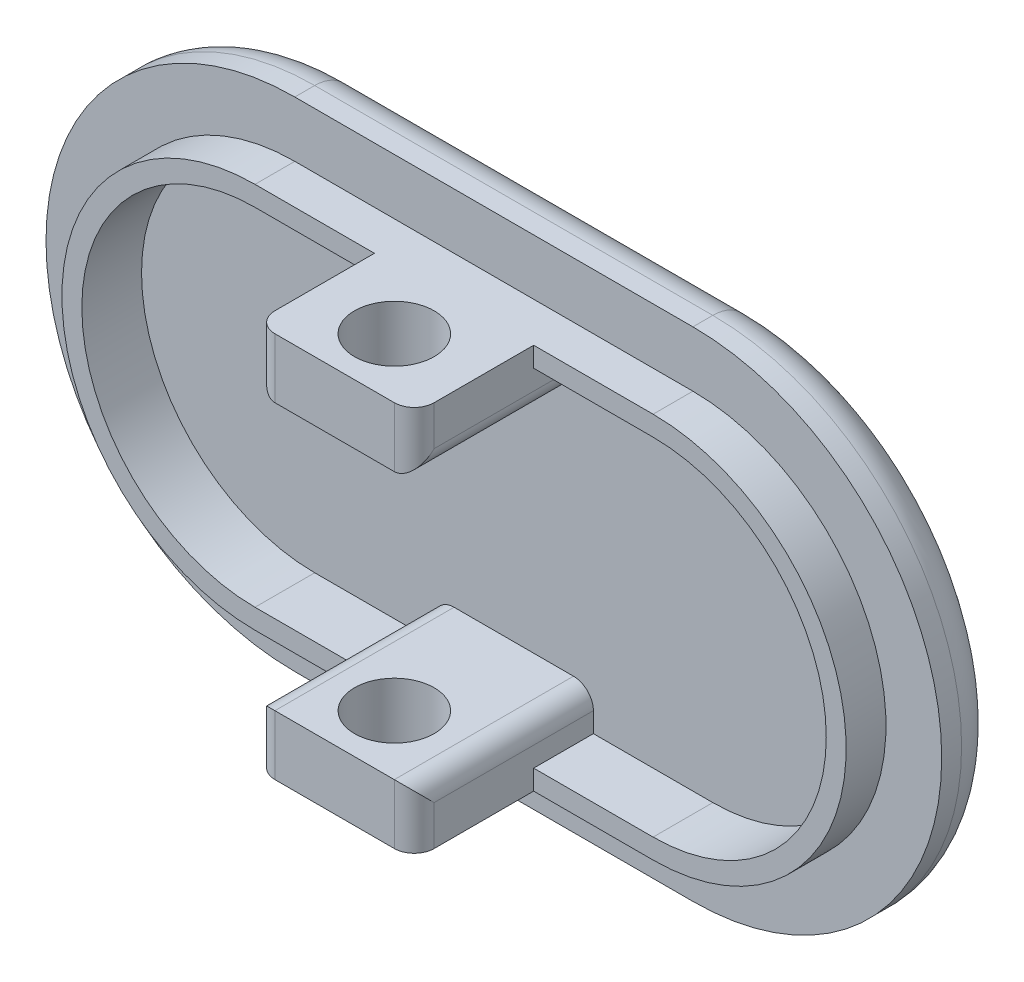
SolidWorks part; units mm, degrees
ref_plane "Plano frontal" through (0, 0, 0) normal (0, 0, 1) x (1, 0, 0)
ref_plane "Plano superior" through (0, 0, 0) normal (0, 1, 0) x (1, 0, 0)
ref_plane "Plano direito" through (0, 0, 0) normal (1, 0, 0) x (0, 0, -1)
sketch "Esboço1" plane through (0, 0, 0) normal (0, 0, 1) x (1, 0, 0)
  line L0 (-10, 0) -> (10, 0) construction
  line L1 (-10, 9.7) -> (10, 9.7)
  line L2 (-10, -9.7) -> (10, -9.7)
  line L3 (-10, 12.5) -> (10, 12.5)
  line L4 (-10, -12.5) -> (10, -12.5)
  arc A0 (-10, 9.7) -> (-10, -9.7) centre (-10, 0) ccw
  arc A1 (10, -9.7) -> (10, 9.7) centre (10, 0) ccw
  arc A2 (10, -12.5) -> (10, 12.5) centre (10, 0) ccw
  arc A3 (-10, 12.5) -> (-10, -12.5) centre (-10, 0) ccw
  point P2 (0, 0)
  dimension "D2" = 9.7
  dimension "D1" = 12.5
  dimension "D3" = 20
extrude "Ressalto-extrusão1" add sketch "Esboço1" along normal blind 3
extrude "Ressalto-extrusão2" add sketch "Esboço1<2>" along normal blind 11 contours L2 A1 L1 A0 region at (0, 0, 0)
sketch "Esboço1<2>" plane through (0, 0, 0) normal (0, 0, 1) x (1, 0, 0) same geometry as "Esboço1"
sketch "Esboço2" plane through (0, 0, 11) normal (0, 0, 1) x (1, 0, 0)
  line L0 (0, 12.5) -> (0, 0) construction
  line L1 (-10, -9.7) -> (-4, -9.7)
  line L2 (-10, -9.7) -> (10, -9.7) construction
  line L3 (-4, -9.7) -> (-4, -6.7)
  line L4 (-4, -6.7) -> (4, -6.7)
  line L5 (-10, 9.7) -> (-4, 9.7)
  line L6 (-4, 9.7) -> (-4, 6.7)
  line L7 (-4, 6.7) -> (4, 6.7)
  line L8 (10, 12.5) -> (-10, 12.5) construction
  line L9 (4, 9.7) -> (4, 6.7)
  line L10 (10, 9.7) -> (4, 9.7)
  line L11 (4, -9.7) -> (4, -6.7)
  line L12 (10, -9.7) -> (4, -9.7)
  arc A0 (-10, 9.7) -> (-10, -9.7) centre (-10, 0) ccw
  arc A3 (10, 9.7) -> (10, -9.7) centre (10, 0) cw
  circle A4 centre (-8.5, 0) radius 8.5 construction
  circle A5 centre (8.5, 0) radius 8.5 construction
  point P24 (0, 6.7)
  point P26 (0, -6.7)
  point P27 (-8.6842, 0)
  point P30 (-8.5, 0)
  point P31 (8.5, 0)
  dimension "D1" = 17
  dimension "D2" = 3
  dimension "D3" = 8
extrude "Corte-extrusão1" cut sketch "Esboço2" against normal offset from surface (6 mm away) 2 up to face at (0, 0, 3)
sketch "Esboço3" plane through (0, -9.7, 0) normal (0, -1, 0) x (1, 0, 0)
  line L0 (-10, 3) -> (10, 3) construction
  circle A0 centre (0, 8) radius 2
  point P2 (0, 0)
  dimension "D1" = 4
  dimension "D2" = 5
extrude "Corte-extrusão2" cut sketch "Esboço3" against normal through all
fillet "Filete1" radius 1 8 edges at (-4, -6.7, 8) (4, -6.7, 8) (-4, 6.7, 8) (4, 6.7, 8) (-4, -8.2, 11) (4, -8.2, 11) (4, 8.2, 11) (-4, 8.2, 11)
fillet "Filete2" radius 2 4 edges at (0, -12.5, 0) (-22.5, 0, 0) (0, 12.5, 0) (22.5, 0, 0)
sketch "Esboço4" plane through (0, 0, 5) normal (0, 0, 1) x (1, 0, 0)
  line L0 (-10, -8.7) -> (-4, -8.7)
  line L4 (4, -8.7) -> (10, -8.7)
  line L5 (10, 8.7) -> (4, 8.7)
  line L9 (-4, 8.7) -> (-10, 8.7)
  line L10 (-10, -9.7) -> (-4, -9.7)
  line L11 (-4, -9.7) -> (-4, -7.7)
  line L12 (-3, -6.7) -> (3, -6.7)
  line L13 (4, -7.7) -> (4, -9.7)
  line L14 (4, -9.7) -> (10, -9.7)
  line L15 (10, 9.7) -> (4, 9.7)
  line L16 (4, 9.7) -> (4, 7.7)
  line L17 (3, 6.7) -> (-3, 6.7)
  line L18 (-4, 7.7) -> (-4, 9.7)
  line L19 (-4, 9.7) -> (-10, 9.7)
  line L20 (-10, -9.7) -> (-4, -9.7) construction
  line L21 (-4, -8.7) -> (-4, -7.7)
  line L22 (-3, -6.7) -> (3, -6.7)
  line L23 (4, -7.7) -> (4, -8.7)
  line L24 (4, -9.7) -> (10, -9.7) construction
  line L25 (10, 9.7) -> (4, 9.7) construction
  line L26 (4, 8.7) -> (4, 7.7)
  line L27 (3, 6.7) -> (-3, 6.7)
  line L28 (-4, 7.7) -> (-4, 8.7)
  line L29 (-4, 9.7) -> (-10, 9.7) construction
  line L30 (-10, -8.7) -> (-5, -8.7) construction
  line L31 (5, -8.7) -> (10, -8.7) construction
  line L32 (10, 8.7) -> (5, 8.7) construction
  line L33 (-5, 8.7) -> (-10, 8.7) construction
  line L34 (4, 9.7) -> (4, 7.7) construction
  line L35 (-4, -9.7) -> (-4, -7.7) construction
  line L36 (4, -7.7) -> (4, -9.7) construction
  line L37 (-4, 7.7) -> (-4, 9.7) construction
  line L40 (-5, 7.7) -> (-5, 8.7) construction
  line L41 (3, 5.7) -> (-3, 5.7) construction
  line L42 (5, 8.7) -> (5, 7.7) construction
  line L43 (-3, -5.7) -> (3, -5.7) construction
  line L44 (5, -7.7) -> (5, -8.7) construction
  line L45 (-5, -8.7) -> (-5, -7.7) construction
  arc A2 (10, -8.7) -> (10, 8.7) centre (10, 0) ccw
  arc A5 (-10, 8.7) -> (-10, -8.7) centre (-10, 0) ccw
  arc A6 (-10, 9.7) -> (-10, -9.7) centre (-10, 0) ccw
  arc A7 (-3, -6.7) -> (-4, -7.7) centre (-3, -7.7) ccw
  arc A8 (4, -7.7) -> (3, -6.7) centre (3, -7.7) ccw
  arc A9 (10, -9.7) -> (10, 9.7) centre (10, 0) ccw
  arc A10 (3, 6.7) -> (4, 7.7) centre (3, 7.7) ccw
  arc A11 (-4, 7.7) -> (-3, 6.7) centre (-3, 7.7) ccw
  arc A12 (-10, 9.7) -> (-10, -9.7) centre (-10, 0) ccw construction
  arc A13 (-3, -6.7) -> (-4, -7.7) centre (-3, -7.7) ccw
  arc A14 (4, -7.7) -> (3, -6.7) centre (3, -7.7) ccw
  arc A15 (10, -9.7) -> (10, 9.7) centre (10, 0) ccw construction
  arc A16 (3, 6.7) -> (4, 7.7) centre (3, 7.7) ccw
  arc A17 (-4, 7.7) -> (-3, 6.7) centre (-3, 7.7) ccw
  arc A24 (-5, 7.7) -> (-3, 5.7) centre (-3, 7.7) ccw construction
  arc A25 (3, 5.7) -> (5, 7.7) centre (3, 7.7) ccw construction
  arc A26 (5, -7.7) -> (3, -5.7) centre (3, -7.7) ccw construction
  arc A27 (-3, -5.7) -> (-5, -7.7) centre (-3, -7.7) ccw construction
  dimension "D1" = 0
  dimension "D2" = 1
extrude "Corte-extrusão3" cut sketch "Esboço4" against normal blind 3
